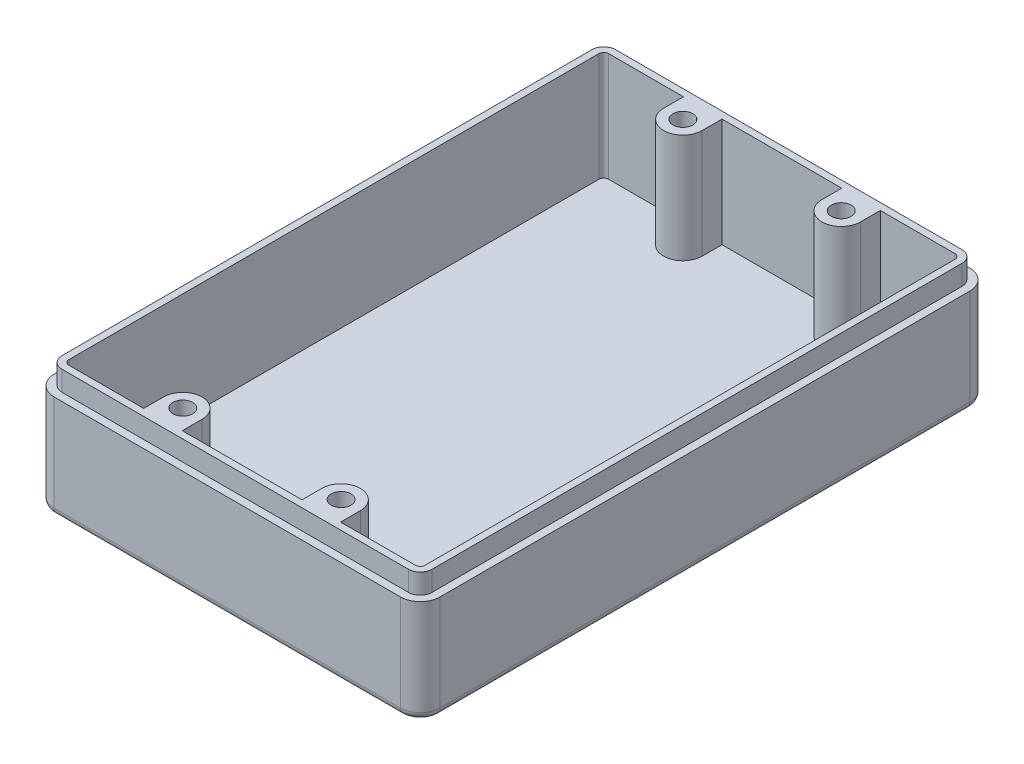
SolidWorks part; units mm, degrees
ref_plane "Plan de face" through (0, 0, 0) normal (0, 0, 1) x (1, 0, 0)
ref_plane "Plan de dessus" through (0, 0, 0) normal (0, 1, 0) x (1, 0, 0)
ref_plane "Plan de droite" through (0, 0, 0) normal (1, 0, 0) x (0, 0, -1)
sketch "Esquisse1" plane through (0, 0, 0) normal (0, 1, 0) x (1, 0, 0)
  line L1 (-39, 0) -> (39, 0)
  line L2 (-39, 0) -> (-39, 115.1)
  line L3 (-39, 115.1) -> (39, 115.1)
  line L4 (39, 0) -> (39, 115.1)
  point P4 (33.289, 0)
  dimension "D1" = 78
  dimension "D2" = 115.1
extrude "Top_Volume" add sketch "Esquisse1" along normal blind 25
fillet "Corner_Radius" radius 4 4 edges at (-39, 12.5, -115.1) (39, 12.5, -115.1) (39, 12.5, 0) (-39, 12.5, 0)
shell "Inside_Hole" thickness 3 removed face at (0, 25, -57.55)
sketch "Esquisse2" plane through (0, 25, 0) normal (0, 1, 0) x (1, 0, 0)
  line L8 (35, 113.5) -> (-35, 113.5)
  line L9 (-37.4, 111.1) -> (-37.4, 4)
  line L10 (-35, 1.6) -> (35, 1.6)
  line L11 (37.4, 4) -> (37.4, 111.1)
  line L12 (35, 113.5) -> (-35, 113.5)
  line L13 (-37.4, 111.1) -> (-37.4, 4)
  line L14 (-35, 1.6) -> (35, 1.6)
  line L15 (37.4, 4) -> (37.4, 111.1)
  arc A8 (-35, 113.5) -> (-37.4, 111.1) centre (-35, 111.1) ccw
  arc A9 (-35, 113.5) -> (-37.4, 111.1) centre (-35, 111.1) ccw
  arc A10 (-37.4, 4) -> (-35, 1.6) centre (-35, 4) ccw
  arc A11 (-37.4, 4) -> (-35, 1.6) centre (-35, 4) ccw
  arc A12 (35, 1.6) -> (37.4, 4) centre (35, 4) ccw
  arc A13 (35, 1.6) -> (37.4, 4) centre (35, 4) ccw
  arc A14 (37.4, 111.1) -> (35, 113.5) centre (35, 111.1) ccw
  arc A15 (37.4, 111.1) -> (35, 113.5) centre (35, 111.1) ccw
  dimension "D1" = 1.6
extrude "Border_Notch" cut sketch "Esquisse2" against normal blind 4.05 flip side to cut
sketch "Esquisse3" plane through (0, 3, 0) normal (0, 1, 0) x (1, 0, 0)
  line L0 (-19.9, 3) -> (-19.9, 7)
  line L1 (-35, 3) -> (35, 3) construction
  line L2 (-19.9, 3) -> (-12.1, 3)
  line L3 (-12.1, 3) -> (-12.1, 7)
  line L4 (-19.9, 7) -> (-12.1, 7) construction
  line L5 (-36, 57.55) -> (36, 57.55) construction
  line L6 (-36, 111.1) -> (-36, 4) construction
  line L7 (36, 4) -> (36, 111.1) construction
  line L8 (-19.9, 112.1) -> (-12.1, 112.1)
  line L9 (-19.9, 112.1) -> (-19.9, 108.1)
  line L10 (-12.1, 112.1) -> (-12.1, 108.1)
  arc A0 (-19.9, 7) -> (-12.1, 7) centre (-16, 7) cw
  circle A2 centre (-16, 7) radius 2
  circle A3 centre (-16, 108.1) radius 2
  arc A4 (-19.9, 108.1) -> (-12.1, 108.1) centre (-16, 108.1) ccw
  dimension "D4" = 4
  dimension "D2" = 4
  dimension "D3" = 16
extrude "Fixation_Col" add sketch "Esquisse3" along normal blind 22
mirror "Symétrie2" about plane through (0, 0, 0) normal (1, 0, 0) of "Fixation_Col"
fillet "Congé2" radius 1.5 8 edges at (-37.8284, 0, -1.1716) (0, 0, 0) (37.8284, 0, -1.1716) (39, 0, -57.55) (37.8284, 0, -113.9284) (0, 0, -115.1) (-37.8284, 0, -113.9284) (-39, 0, -57.55)
sketch "Esquisse4" plane through (0, 0, 0) normal (0, -1, 0) x (1, 0, 0)
  line L0 (-37.5, -4) -> (-37.5, -57.55) construction
  line L1 (-37.5, -4) -> (-37.5, -111.1) construction
  line L2 (-37.5, -57.55) -> (37.5, -57.55) construction
  line L3 (37.5, -111.1) -> (37.5, -4) construction
  line L4 (37.5, -57.55) -> (37.5, -4) construction
  line L5 (37.5, -4) -> (-37.5, -4) construction
  line L6 (-37.5, -57.55) -> (-37.5, -111.1) construction
  line L7 (-37.5, -111.1) -> (37.5, -111.1) construction
  line L8 (37.5, -111.1) -> (37.5, -57.55) construction
  line L9 (-37.5, -84.325) -> (37.5, -84.325) construction
  line L10 (-37.5, -30.775) -> (37.5, -30.775) construction
  text T0 "<b>ETML-ES</b>\r\n<b>SLO2-23</b>" font "Century Gothic" height 8
  text T1 "2228 Alarme fenêtre V1" font "Century Gothic" height 4
  text T2 "\r\nMiguel Santos" font "Century Gothic" height 6
extrude "Enlèv. mat.-Extru.2" cut sketch "Esquisse4" against normal blind 0.4
equation "\"PCB_Length_Y\"= 60mm"
equation "\"PCB_Width_X\"= 60mm"
equation "\"PCB_Thickness_Z\"= 1.55mm"
equation "\"PCB_Pos_Y\"= 5mm"
equation "\"PCB_Zone_Y\"= \"PCB_Length_Y\" + \"Box_Wall_Thickness\" 'Zone occupée par le PCB centrée au milieu de la zone"
equation "\"PCB_Zone_X\"= \"PCB_Width_X\" + 12mm"
equation "\"Battery_Zone_Y\"= \"Battery_Length_Y\" + \"Box_Wall_Thickness\" + \"Fixation_holes_offset\" + \"Col_Diameter\"/2 + \"Battery_Offset\" + \"Global_Gap\"*2"
equation "\"Battery_Length_Y\"= 25mm"
equation "\"Battery_Width_X\"= 55mm"
equation "\"Box_Wall_Thickness\"= 3mm"
equation "\"Box_Border_Height\"= \"Col_Height\" + \"PCB_Thickness_Z\""
equation "\"Box_Corner_Radius\"= 4mm"
equation "\"PCB_Holes_X\"= 52mm"
equation "\"PCB_Holes_Y\"= 52mm"
equation "\"Col_Height\"= 2.5mm"
equation "\"Box_Bottom_Thick\"= 3mm"
equation "\"Box_Top_Thick\"= 3mm"
equation "\"PCB_Components_Height\"= 22mm"
equation "\"Global_Gap\"= 0.1mm"
equation "\"Col_Diameter\"= 7.8mm"
equation "\"D1@Esquisse1\"=\"PCB_Zone_X\"+2 * \"Box_Wall_Thickness\""
equation "\"D2@Esquisse1\"=2 * \"Box_Wall_Thickness\" + \"PCB_Zone_Y\" + \"Battery_Zone_Y\""
equation "\"Inserts_Diameter\"= 4mm"
equation "\"Inserts_Height\"= 4mm"
equation "\"Fixation_holes_X\"= 32mm"
equation "\"Fixation_holes_offset\"= 4mm'Distance from inside border of hole center"
equation "\"Solar_Width_X\"= 23.4mm"
equation "\"Solar_Length_Y\"= 8.4mm"
equation "\"D1@Corner_Radius\" = \"Box_Corner_Radius\""
equation "\"D1@Inside_Hole\"=\"Box_Wall_Thickness\""
equation "\"D2@Inside_Hole\"= \"Box_Bottom_Thick\""
equation "\"D1@Border_Notch\" = \"Box_Border_Height\""
equation "\"D1@Esquisse2\"=\"Box_Wall_Thickness\"/2 + \"Global_Gap\""
equation "\"D1@Fixation_Col\"= \"PCB_Components_Height\""
equation "\"D3@Esquisse3\"=(\"PCB_Zone_Y\" - \"PCB_Holes_Y\")/2 + \"Box_Wall_Thickness\""
equation "\"D4@Esquisse3\"=\"Inserts_Diameter\""
equation "\"D1@Congé2\"=\"Box_Bottom_Thick\"/2"
equation "\"D1@Top_Volume\"=\"Box_Top_Thick\"+\"PCB_Components_Height\""
equation "\"D1@Enlèv. mat.-Extru.2\"=0.4mm"
equation "\"PCB_Zone_X\"= 64mm"
equation "\"Battery_Zone_Y\"= \"Battery_Length_Y\" + \"Box_Wall_Thickness\" + \"Fixation_holes_offset\" + \"Col_Diameter\"/2 + \"Battery_Offset\""
equation "\"Battery_Width_X\"= 54mm"
equation "\"Col_Height\"= 4mm"
equation "\"Box_Bottom_Thick\"= 4mm"
equation "\"Box_Top_Thick\"= 4mm"
equation "\"PCB_Components_Height\"= 25mm"
equation "\"Col_Diameter\"= 8mm"
equation "\"D1@Esquisse3\"=\"Col_Diameter\""
equation "\"D2@Esquisse3\"=\"Fixation_holes_offset\""
equation "\"D3@Esquisse3\"=\"Fixation_holes_X\" / 2"
equation "\"Inserts_Height\"= 5mm"
equation "\"Battery_Offset\"= 10mm"
